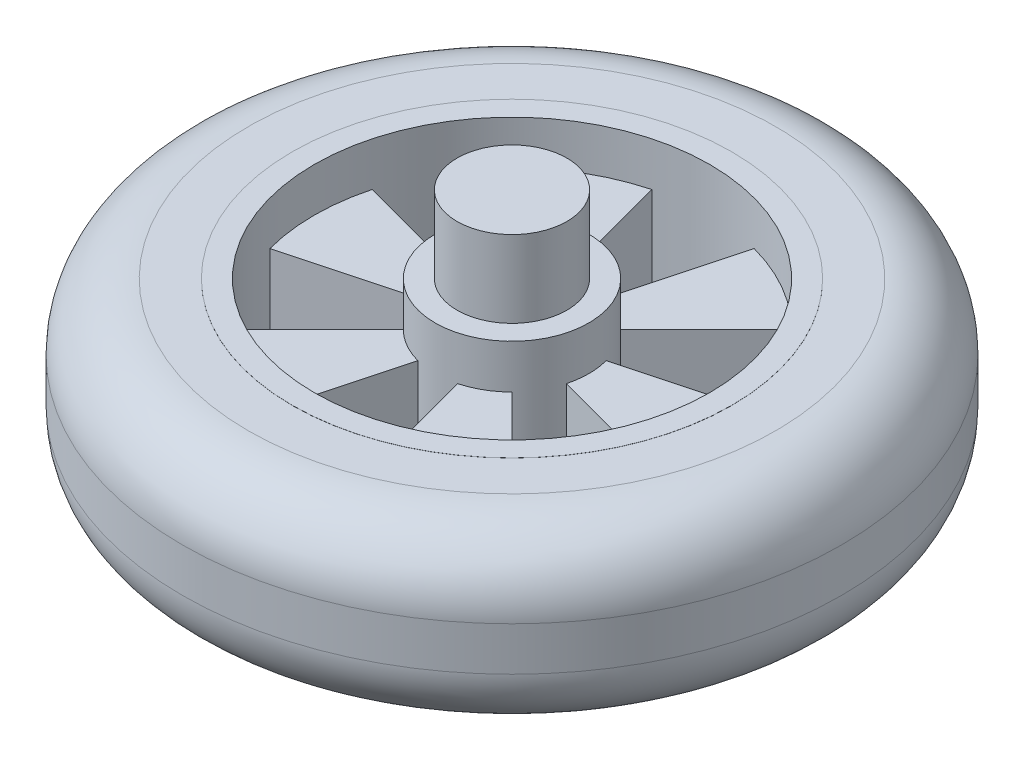
SolidWorks part; units mm, degrees
ref_plane "前视基准面" through (0, 0, 0) normal (0, 0, 1) x (1, 0, 0)
ref_plane "上视基准面" through (0, 0, 0) normal (0, 1, 0) x (1, 0, 0)
ref_plane "右视基准面" through (0, 0, 0) normal (1, 0, 0) x (0, 0, -1)
sketch "草图1" plane through (0, 0, 0) normal (0, 1, 0) x (1, 0, 0)
  circle A0 centre (0, 0) radius 5
  dimension "D1" = 10
extrude "凸台-拉伸1" add sketch "草图1" along normal blind 15 and the other way blind 15
sketch "草图2" plane through (0, 0, 0) normal (0, 1, 0) x (1, 0, 0)
  circle A0 centre (0, 0) radius 20
  dimension "D1" = 40
extrude "凸台-拉伸2" add sketch "草图2" along normal blind 8 and the other way blind 8
sketch "草图4" plane through (0, 8, 0) normal (0, 1, 0) x (1, 0, 0)
  circle A0 centre (0, 0) radius 7
  circle A1 centre (0, 0) radius 18
  dimension "D1" = 14
  dimension "D2" = 36
extrude "切除-拉伸1" cut sketch "草图4" against normal blind 4
mirror "镜向1" about plane through (0, 0, 0) normal (0, 1, 0) of "切除-拉伸1"
sketch "草图5" plane through (0, 4, 0) normal (0, 1, 0) x (1, 0, 0)
  line L0 (0, 18) -> (0, 0) construction
  line L1 (0, 0) -> (1.8117, 6.7615) construction
  line L2 (0, 0) -> (-1.8117, 6.7615) construction
  line L3 (-1.8117, 6.7615) -> (-4.6587, 17.3867)
  line L4 (1.8117, 6.7615) -> (4.6587, 17.3867)
  circle A0 centre (0, 0) radius 18 construction
  circle A1 centre (0, 0) radius 18 construction
  circle A2 centre (0, 0) radius 7 construction
  arc A3 (1.8117, 6.7615) -> (-1.8117, 6.7615) centre (0, 0) ccw
  arc A4 (4.6587, 17.3867) -> (-4.6587, 17.3867) centre (0, 0) ccw
  dimension "D1" = 15
  dimension "D2" = 15
  dimension "D3" = 15
extrude "切除-拉伸2" cut sketch "草图5" against normal blind 14
pattern_circular "阵列(圆周)1" count 6 over 360 about axis through (0, -15, 0) along (0, 1, 0) of "切除-拉伸2" reverse direction yes
sketch "草图6" plane through (0, 0, 0) normal (0, 1, 0) x (1, 0, 0)
  circle A0 centre (0, 0) radius 20
  circle A1 centre (0, 0) radius 30
  dimension "D1" = 40
  dimension "D2" = 60
extrude "凸台-拉伸3" add sketch "草图6" along normal blind 7.99 and the other way blind 7.99
fillet "圆角1" radius 6 2 edges at (0, 7.99, 30) (0, -7.99, 30)
